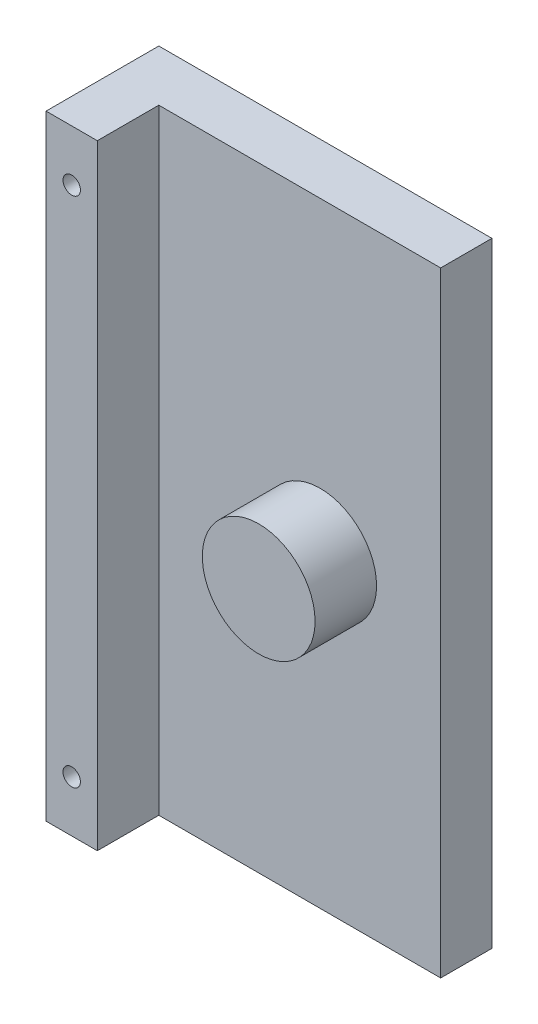
SolidWorks part; units mm, degrees
ref_plane "Front Plane" through (0, 0, 0) normal (1, 0, 0) x (0, 1, 0)
ref_plane "Top Plane" through (0, 0, 0) normal (0, 0, 1) x (0, 1, 0)
ref_plane "Right Plane" through (0, 0, 0) normal (0, 1, 0) x (-1, 0, 0)
sketch "Sketch1" plane through (0, 0, 0) normal (0, 0, 1) x (0, 1, 0)
  line L1 (60, -32.5) -> (-60, -32.5)
  line L2 (60, -32.5) -> (60, 32.5)
  line L3 (60, 32.5) -> (-60, 32.5)
  line L4 (-60, -32.5) -> (-60, 32.5)
  line L5 (60, -32.5) -> (-60, 32.5) construction
  line L6 (60, 32.5) -> (-60, -32.5) construction
  point P0 (0, 0)
  dimension "D1" = 65
  dimension "D2" = 120
extrude "Boss-Extrude1" add sketch "Sketch1" along normal blind 10
sketch "Sketch2" plane through (0, 0, 10) normal (0, 0, 1) x (1, 0, 0)
  line L0 (-32.5, -60) -> (32.5, -60) construction
  line L1 (-32.5, 60) -> (-22.5, 60)
  line L2 (-32.5, 60) -> (-32.5, -60)
  line L3 (-32.5, -60) -> (-22.5, -60)
  line L4 (-22.5, 60) -> (-22.5, -60)
  dimension "D1" = 10
extrude "Boss-Extrude2" add sketch "Sketch2" along normal blind 12
sketch "Sketch3" plane through (0, 0, 10) normal (0, 0, 1) x (1, 0, 0)
  line L0 (-22.5, -60) -> (32.5, -60) construction
  line L1 (32.5, -60) -> (32.5, 60) construction
  circle A0 centre (8.99, 0) radius 11
  dimension "D1" = 22
  dimension "D2" = 60
  dimension "D3" = 23.51
extrude "Boss-Extrude3" add sketch "Sketch3" along normal blind 12
sketch "Sketch4" plane through (0, 0, 22) normal (0, 0, 1) x (1, 0, 0)
  line L0 (-32.5, -60) -> (-22.5, -60) construction
  line L1 (-22.5, 60) -> (-32.5, 60) construction
  line L2 (-32.5, 60) -> (-32.5, -60) construction
  circle A0 centre (-27.5, 50) radius 1.7
  circle A1 centre (-27.5, -50) radius 1.7
  dimension "D1" = 3.4
  dimension "D2" = 3.4
  dimension "D3" = 10
  dimension "D4" = 10
  dimension "D5" = 5
  dimension "D6" = 5
extrude "Cut-Extrude1" cut sketch "Sketch4" against normal blind 22
